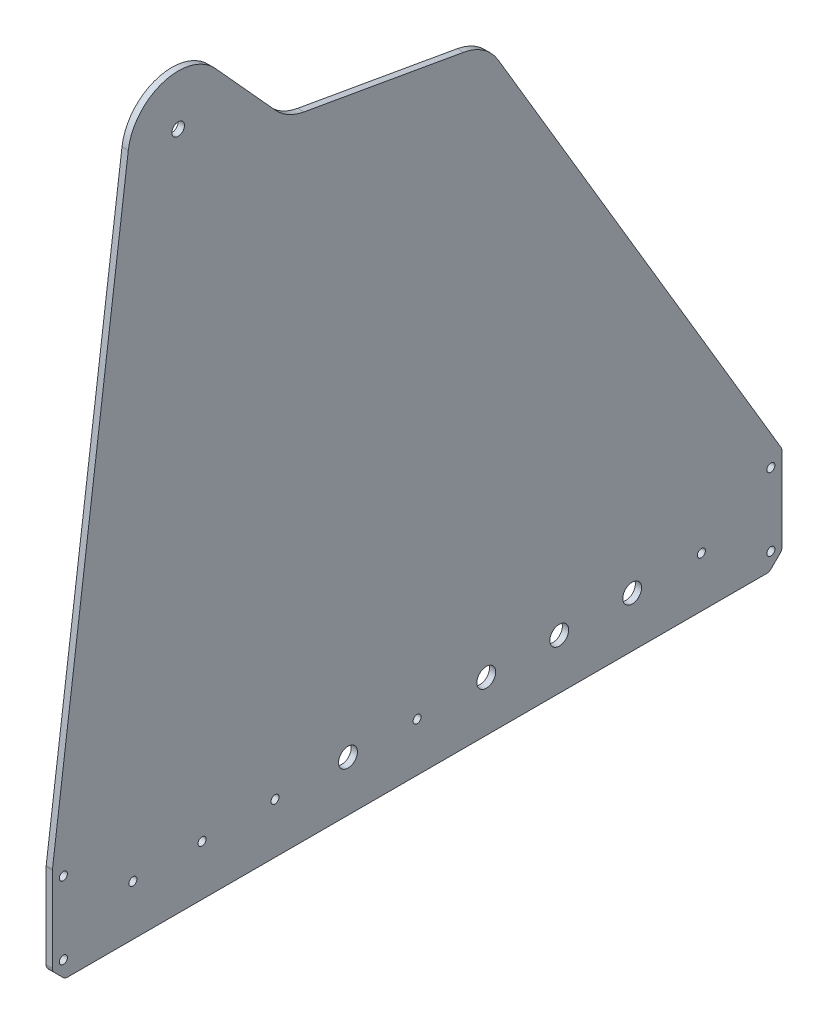
SolidWorks part; units mm, degrees
ref_plane "Front Plane" through (0, 0, 0) normal (0, 0, 1) x (1, 0, 0)
ref_plane "Top Plane" through (0, 0, 0) normal (0, 1, 0) x (1, 0, 0)
ref_plane "Right Plane" through (0, 0, 0) normal (1, 0, 0) x (0, 0, -1)
sketch "Sketch2" plane through (0, 0, 0) normal (1, 0, 0) x (0, 0, -1)
  line L0 (0, 0) -> (0, 50.8)
  line L1 (0, 50.8) -> (38.311, 346.1672)
  line L4 (368.3, 50.8) -> (368.3, 0)
  line L5 (368.3, 0) -> (0, 0)
  line L7 (225.0471, 292.3562) -> (368.3, 50.8)
  line L8 (368.3, 50.8) -> (419.4553, 50.8) construction
  line L9 (0, 374.65) -> (368.3, 374.65) construction
  line L10 (82.3138, 359.9646) -> (112.5969, 326.5774)
  line L11 (127, 318.628) -> (207.6107, 304.4141)
  arc A0 (38.311, 346.1672) -> (82.3138, 359.9646) centre (63.5, 342.9) cw
  arc A1 (207.6107, 304.4141) -> (225.0471, 292.3562) centre (203.2, 279.4) cw
  arc A3 (112.5969, 326.5774) -> (127, 318.628) centre (131.4107, 343.6421) ccw
  dimension "D6" = 25.4
  dimension "D7" = 25.4
  dimension "D1" = 368.3
  dimension "D2" = 50.8
  dimension "D4" = 304.8
  dimension "D5" = 342.9
  dimension "D8" = 374.65
  dimension "D9" = 279.4
  dimension "D10" = 203.2
  dimension "D11" = 127
  dimension "D12" = 10
extrude "Plate" add sketch "Sketch2" along normal blind 3.175
sketch "Sketch9" plane through (0, 0, 0) normal (1, 0, 0) x (0, 0, -1)
  line L0 (0, 0) -> (368.3, 0) construction
  point P4 (184.15, 0)
  point P5 (184.15, 24.6063)
  dimension "D1" = 24.6062
sketch "Sketch10" plane through (3.175, 0, 0) normal (1, 0, 0) x (0, 0, -1)
  point P0 (149.234, 25.4)
  point P1 (219.066, 25.4)
  point P3 (255.896, 25.4)
  point P5 (292.726, 25.4)
sketch "Sketch12" plane through (3.175, 0, 0) normal (1, 0, 0) x (0, 0, -1)
  line L0 (184.15, 24.6063) -> (219.066, 25.4) construction
  line L1 (219.066, 25.4) -> (255.896, 25.4) construction
  line L2 (292.726, 25.4) -> (327.651, 25.4) construction
  line L3 (149.234, 25.4) -> (112.404, 25.4) construction
  line L4 (112.404, 25.4) -> (75.574, 25.4) construction
  line L5 (75.574, 25.4) -> (40.649, 25.4) construction
  point P0 (184.15, 24.6063)
  point P1 (184.15, 24.6063)
  point P8 (327.651, 25.4)
  point P11 (112.404, 25.4)
  point P15 (75.574, 25.4)
  point P16 (40.649, 25.4)
  point P29 (112.404, 25.4)
  point P31 (75.574, 25.4)
  point P33 (40.649, 25.4)
  point P35 (327.651, 25.4)
hole_wizard "3/8 (0.375) Diameter Hole1" positions "Sketch10" profile "Sketch11" hole size "3/8" standard "ANSI Inch" end condition through all
sketch "Sketch11" plane through (3.175, 25.4, -149.234) normal (0, 1, 0) x (0, 0, -1)
  line L0 (0, 0) -> (0, 3.175)
  line L1 (0, 3.175) -> (4.7625, 3.175)
  line L2 (4.7625, 3.175) -> (4.7625, 0)
  line L5 (4.7625, 0) -> (0, 0)
  line L11 (0, -6.35) -> (0, 107.95) construction
  dimension "Thru Hole Dia." = 9.525
  dimension "Thru Hole Depth" = 3.175
hole_wizard "#8 Clearance Hole1" positions "Sketch12" profile "Sketch13" hole size "#8" standard "ANSI Inch" end condition through all
sketch "Sketch13" plane through (3.175, 24.6063, -184.15) normal (0, 1, 0) x (0, 0, -1)
  line L0 (0, 0) -> (0, 3.175)
  line L1 (0, 3.175) -> (2.032, 3.175)
  line L2 (2.032, 3.175) -> (2.032, 0)
  line L5 (2.032, 0) -> (0, 0)
  line L11 (0, -6.35) -> (0, 107.95) construction
  dimension "Thru Hole Dia." = 4.064
  dimension "Thru Hole Depth" = 3.175
ref_axis "Axis1" through (0, 25.4, -149.234) along (1, 0, 0)
ref_axis "Axis2" through (0, 25.4, -219.066) along (1, 0, 0)
ref_axis "Axis3" through (0, 25.4, -255.896) along (1, 0, 0)
ref_axis "Axis4" through (0, 25.4, -292.726) along (1, 0, 0)
sketch "Sketch3" plane through (3.175, 0, 0) normal (1, 0, 0) x (0, 0, -1)
  circle A0 centre (63.5, 342.9) radius 3.175
  dimension "D1" = 6.35
extrude "Tube Pivot Holes" cut sketch "Sketch3" against normal through all
chamfer "Bottom Corner Chamfer" distance 6.35 angle 45 2 edges at (1.5875, 0, -368.3) (1.5875, 0, 0)
fillet "Bottom Corner Fillet" radius 3.175 6 edges at (1.5875, 50.8, 0) (1.5875, 0, -6.35) (1.5875, 6.35, 0) (1.5875, 0, -361.95) (1.5875, 6.35, -368.3) (1.5875, 50.8, -368.3)
sketch "Sketch7" plane through (3.175, 0, 0) normal (1, 0, 0) x (0, 0, -1)
  point P0 (5.5562, 45.2438)
  point P1 (5.5562, 8.6515)
  point P3 (362.7438, 45.2438)
  point P5 (362.7438, 8.6515)
hole_wizard "Carbon Cap Holes" positions "Sketch7" profile "Sketch8" hole size "#8" standard "ANSI Inch" end condition through all
sketch "Sketch8" plane through (3.175, 45.2438, -5.5562) normal (0, 1, 0) x (0, 0, -1)
  line L0 (0, 0) -> (0, 3.175)
  line L1 (0, 3.175) -> (2.032, 3.175)
  line L2 (2.032, 3.175) -> (2.032, 0)
  line L5 (2.032, 0) -> (0, 0)
  line L11 (0, -6.35) -> (0, 107.95) construction
  dimension "Thru Hole Dia." = 4.064
  dimension "Thru Hole Depth" = 3.175
equation "\"Driven to Driven Gear Spacing\"= ( \"Driven Gear\" / \"DP\" )"
equation "\"Driven to Wheel Gear Spacing\"= ( \"Driven Gear\" / ( \"DP\" * 2 ) ) + ( \"Wheel Gear\" / ( \"DP\" * 2 ) )"
equation "\"Driven Gear\"= 29"
equation "\"Wheel Gear\"= 28"
equation "\"DP\"= 20"
